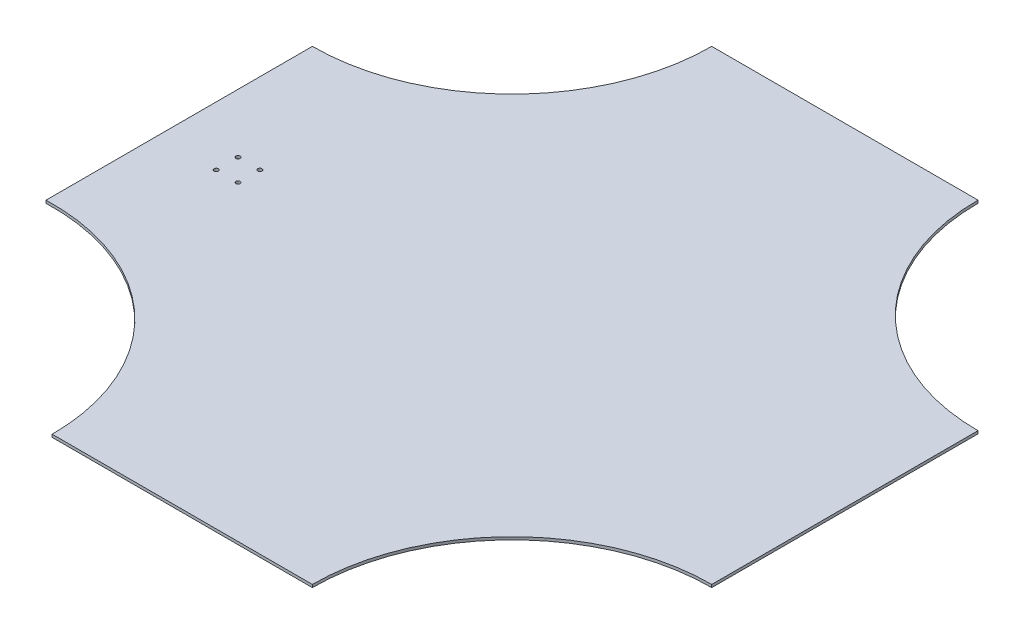
SolidWorks part; units mm, degrees
ref_plane "Front Plane" through (0, 0, 0) normal (0, 0, 1) x (1, 0, 0)
ref_plane "Top Plane" through (0, 0, 0) normal (0, 1, 0) x (1, 0, 0)
ref_plane "Right Plane" through (0, 0, 0) normal (1, 0, 0) x (0, 0, -1)
sketch "Sketch1" plane through (0, 0, 0) normal (0, 1, 0) x (1, 0, 0)
  line L5 (-145.4402, -381) -> (152.4, -381)
  line L6 (-381, -152.506) -> (-381, 152.4)
  line L7 (-152.4, 381) -> (152.4, 381)
  line L8 (381, -152.4) -> (381, 152.4)
  line L9 (-215.913, -215.913) -> (219.3554, 219.3554) construction
  line L10 (-219.3554, 219.3554) -> (219.3554, -219.3554) construction
  arc A4 (-381, 152.4) -> (-152.4, 381) centre (-381, 381) ccw
  arc A5 (-145.4402, -381) -> (-381, -152.506) centre (-374.0402, -381) ccw
  arc A6 (381, -152.4) -> (152.4, -381) centre (381, -381) ccw
  arc A7 (152.4, 381) -> (381, 152.4) centre (381, 381) ccw
  point P0 (0, 0)
  point P1 (0, 0)
  dimension "D3" = 457.2
  dimension "D4" = 457.2
  dimension "D5" = 457.2
  dimension "D6" = 457.2
  dimension "D1" = 762
extrude "Boss-Extrude1" add sketch "Sketch1" along normal blind 3.175
sketch "Sketch2" plane through (0, 3.175, 0) normal (0, 1, 0) x (1, 0, 0)
  circle A0 centre (-313.5959, 0) radius 2.413
  circle A1 centre (-288.5956, 0) radius 2.413
  circle A2 centre (-288.5956, -25.116) radius 2.413
  circle A3 centre (-313.5959, -25.116) radius 2.413
  dimension "D1" = 4.826
  dimension "D2" = 4.826
  dimension "D3" = 4.826
  dimension "D4" = 4.826
extrude "Cut-Extrude1" cut sketch "Sketch2" against normal through all both and the other way through all
